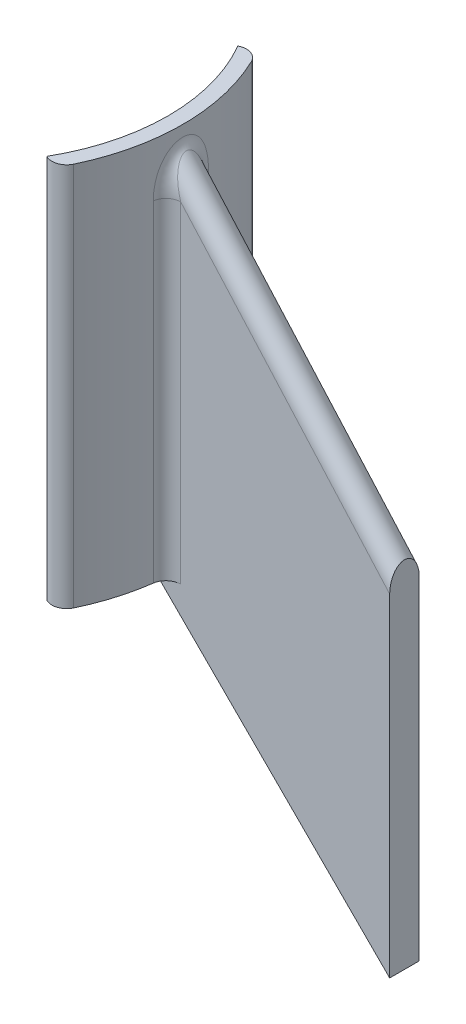
SolidWorks part; units mm, degrees
other "Fin"
ref_plane "Front Plane" through (0, 0, 0) normal (0, 0, 1) x (1, 0, 0)
ref_plane "Top Plane" through (0, 0, 0) normal (0, 1, 0) x (1, 0, 0)
ref_plane "Right Plane" through (0, 0, 0) normal (1, 0, 0) x (0, 0, -1)
sketch "n" plane through (0, 0, 0) normal (0, 0, 1) x (1, 0, 0)
  line L0 (0, 0) -> (0, 41.275)
  line L1 (0, 41.275) -> (25.4, 12.7)
  line L2 (25.4, 12.7) -> (25.4, -25.4)
  line L3 (25.4, -25.4) -> (0, 0)
  dimension "D1" = 25.4
  dimension "D2" = 41.275
  dimension "D3" = 28.575
  dimension "D4" = 66.675
  dimension "D5" = 25.4
extrude "Boss-Extrude1" add sketch "n" along normal blind 1.5875 and the other way blind 1.5875 contours L3 L0 L1 L2
sketch "Sketch1" plane through (0, 0, 0) normal (0, 0, 1) x (1, 0, 0)
  line L0 (0, 0) -> (1.5875, 0)
  line L1 (1.5875, 0) -> (1.5875, 41.275)
  line L2 (1.5875, 41.275) -> (0, 41.275)
  line L3 (0, 41.275) -> (0, 0)
  line L4 (-20.5232, -0.6786) -> (-20.5232, 49.4231) construction
  dimension "D1" = 1.5875
  dimension "D2" = 20.5232
fillet "Fillet1" 2 edges at (12.7, 26.9875, 1.5875) (12.7, 26.9875, -1.5875) type full round first side face at (12.7, 7.1437, 1.5875) second side face at (12.7, 7.1437, -1.5875) middle face at (12.7, 26.9875, 0)
revolve "Revolve1" add sketch "Sketch1" angle 30 about L4 other way angle 30
fillet "Fillet2" radius 1.5875 5 edges at (1.5304, 18.5819, 1.5875) (1.5864, 34.7342, -0.2193) (-1.3748, 20.6375, 11.0554) (-1.3748, 20.6375, -11.0554) (1.5304, 18.5819, -1.5875)
